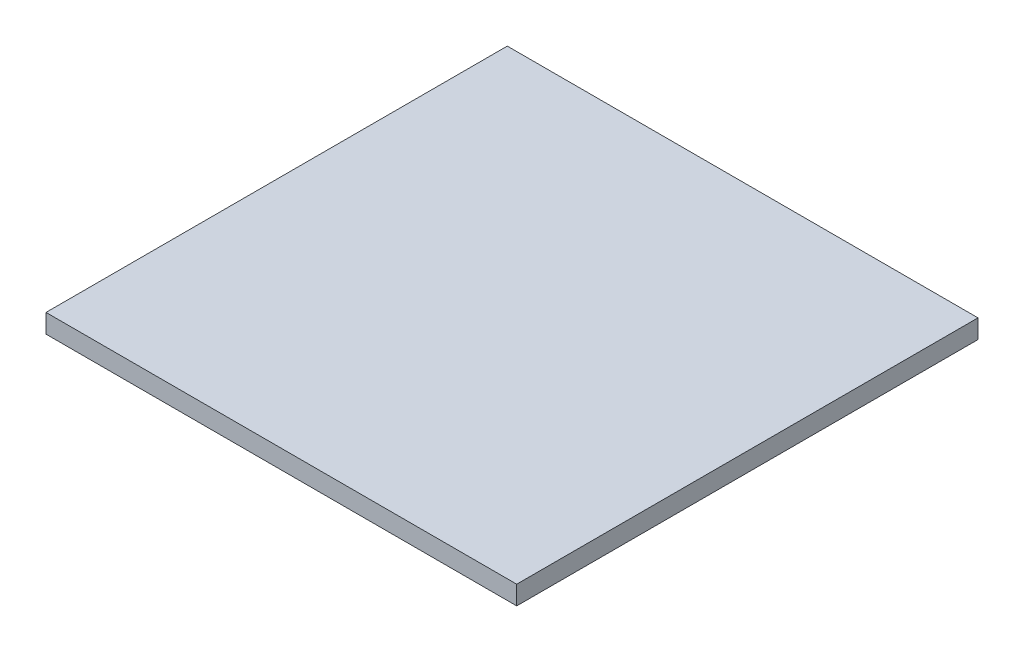
SolidWorks part; units mm, degrees
material "Acrylic (Medium-high impact)"
ref_plane "Front Plane" through (0, 0, 0) normal (0, 0, 1) x (1, 0, 0)
ref_plane "Top Plane" through (0, 0, 0) normal (0, 1, 0) x (1, 0, 0)
ref_plane "Right Plane" through (0, 0, 0) normal (1, 0, 0) x (0, 0, -1)
sketch "Sketch1" plane through (0, 0, 0) normal (0, 1, 0) x (1, 0, 0)
  line L1 (-25, 24.5) -> (25, 24.5)
  line L2 (-25, 24.5) -> (-25, -24.5)
  line L3 (-25, -24.5) -> (25, -24.5)
  line L4 (25, 24.5) -> (25, -24.5)
  line L5 (-25, 24.5) -> (25, -24.5) construction
  line L6 (-25, -24.5) -> (25, 24.5) construction
  point P0 (0, 0)
  dimension "D1" = 49
  dimension "D2" = 50
extrude "Boss-Extrude1" add sketch "Sketch1" along normal mid plane 2
